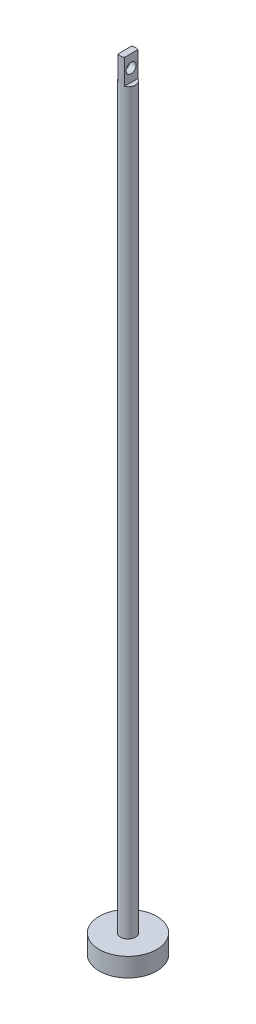
SolidWorks part; units mm, degrees
ref_plane "前视基准面" through (0, 0, 0) normal (0, 0, 1) x (1, 0, 0)
ref_plane "上视基准面" through (0, 0, 0) normal (0, 1, 0) x (1, 0, 0)
ref_plane "右视基准面" through (0, 0, 0) normal (1, 0, 0) x (0, 0, -1)
sketch "草图1" plane through (0, 0, 0) normal (0, 1, 0) x (1, 0, 0)
  circle A0 centre (0, 0) radius 23
  dimension "D1" = 46
extrude "凸台-拉伸1" add sketch "草图1" along normal blind 15
sketch "草图2" plane through (0, 15, 0) normal (0, 1, 0) x (1, 0, 0)
  circle A0 centre (0, 0) radius 6
  dimension "D1" = 12
extrude "凸台-拉伸2" add sketch "草图2" along normal blind 610
sketch "草图3" plane through (0, 625, 0) normal (0, 1, 0) x (1, 0, 0)
  line L1 (-2.5, 10) -> (2.5, 10)
  line L2 (-2.5, 10) -> (-2.5, -10)
  line L3 (-2.5, -10) -> (2.5, -10)
  line L4 (2.5, 10) -> (2.5, -10)
  line L5 (-2.5, 10) -> (2.5, -10) construction
  line L6 (-2.5, -10) -> (2.5, 10) construction
  point P0 (0, 0)
  point P1 (0, 0)
  dimension "D1" = 5
  dimension "D2" = 20
extrude "切除-拉伸1" cut sketch "草图3" against normal blind 20 flip side to cut
ref_plane "基准面1" through (-2.5, 0, 0) normal (-1, 0, 0) x (0, 0, 1)
sketch "草图4" plane through (-2.5, 0, 0) normal (-1, 0, 0) x (0, 0, 1)
  line L0 (0, 0) -> (0, 362.7684) construction
  line L4 (-5.4544, 615) -> (5.4544, 615)
  line L5 (-5.4544, 615) -> (5.4544, 615) construction
  circle A0 centre (0, 615) radius 4
  point P8 (0, 615)
  point P9 (0, 0)
  point P10 (0, 0)
  dimension "D2" = 8
  dimension "D1" = 10
extrude "切除-拉伸2" cut sketch "草图4" against normal blind 20
